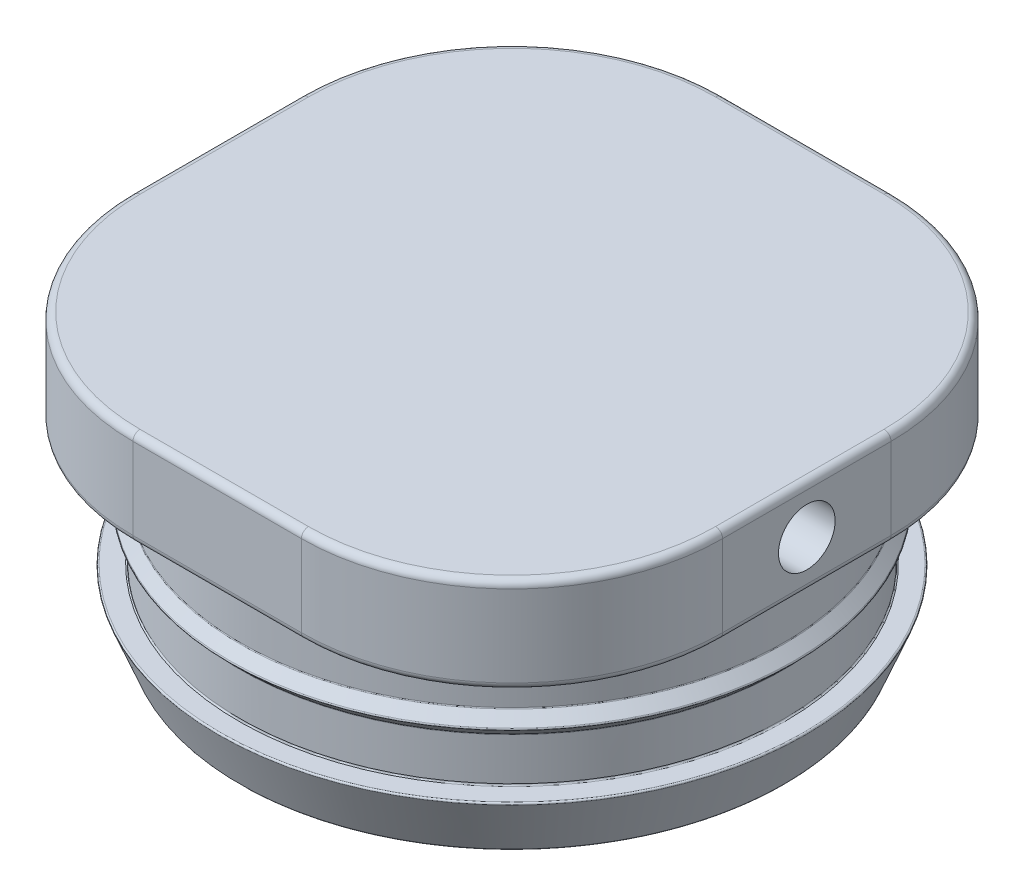
SolidWorks part; units mm, degrees
ref_plane "Front Plane" through (0, 0, 0) normal (0, 0, 1) x (1, 0, 0)
ref_plane "Top Plane" through (0, 0, 0) normal (0, 1, 0) x (1, 0, 0)
ref_plane "Right Plane" through (0, 0, 0) normal (1, 0, 0) x (0, 0, -1)
sketch "Sketch1" plane through (0, 0, 0) normal (0, 0, 1) x (1, 0, 0)
  line L3 (0, 0) -> (0, -6.8) construction
  line L4 (-21, 0) -> (0, 0)
  line L5 (-21, 0) -> (-21, -6.8)
  line L6 (-21, -6.8) -> (21, -6.8)
  line L7 (21, 0) -> (21, -6.8)
  line L8 (0, 0) -> (21, 0)
  dimension "D4" = 42
  dimension "D5" = 6.8
extrude "Boss-Extrude1" add sketch "Sketch1" along normal mid plane 42
sketch3d "3DSketch1" plane through (0, 0, 0) normal (0, 0, 1) x (1, 0, 0)
  dimension "D1" = 12.7
sketch "Sketch2" plane through (0, 0, 0) normal (0, 0, 1) x (1, 0, 0)
  line L0 (0, 9.544) -> (0, -9.544) construction
  line L1 (0, -6.8) -> (19.365, -6.8)
  line L4 (0, -19.5) -> (19.365, -19.5)
  line L10 (0, -19.5) -> (0, -6.8)
  line L11 (19.365, -19.5) -> (20.9525, -15.5312)
  line L12 (20.9525, -15.5312) -> (19.365, -15.5312)
  line L13 (19.365, -15.5312) -> (19.365, -12.3562)
  line L14 (19.365, -12.3562) -> (20.1588, -11.5625)
  line L15 (20.1588, -11.5625) -> (19.365, -10.7687)
  line L16 (20.1588, -11.5625) -> (19.365, -11.5625) construction
  line L17 (19.365, -10.7687) -> (19.365, -6.8)
  dimension "D1" = 38.73
  dimension "D2" = 12.7
  dimension "D3" = 1.5875
  dimension "D4" = 3.9688
  dimension "D5" = 0.7937
  dimension "D6" = 7.9375
  dimension "D7" = 6.8
revolve "Revolve1" add sketch "Sketch2" angle 360 about L0
sketch "Sketch3" plane through (0, -19.5, 0) normal (0, -1, 0) x (1, 0, 0)
  circle A0 centre (0, 0) radius 4
  dimension "D1" = 8
extrude "Cut-Extrude1" cut sketch "Sketch3" against normal blind 18.5 contours A0
hole_wizard "#10-32 Tapped Hole1" positions "Sketch4" profile "Sketch5" tap size "#10-32" standard "ANSI Inch" end condition up to next
sketch "Sketch4" plane through (21, 0, 0) normal (1, 0, 0) x (0, 0, -1)
  point P0 (0, -3.4)
  dimension "D1" = 3.4
cosmetic thread "Hole Thread1" parameters "D2"=4.826
sketch "Sketch5" plane through (21, -3.4, 0) normal (0, 1, 0) x (0, 0, -1)
  line L0 (0, 0) -> (0, 17)
  line L1 (0, 17) -> (2.0193, 17)
  line L2 (2.0193, 17) -> (2.0193, 0)
  line L5 (2.0193, 0) -> (0, 0)
  line L11 (0, -6.35) -> (0, 107.95) construction
  dimension "Thru Tap Drill Dia." = 4.0386
  dimension "Thru Tap Drill Depth" = 17
fillet "Fillet3" radius 0.1 8 edges at (-20.9525, -15.5313, 0) (-20.1588, -11.5625, 0) (4, -1, 0) (-19.365, -19.5, 0) (-19.365, -6.8, 0) (-19.365, -10.7688, 0) (-19.365, -12.3563, 0) (-19.365, -15.5313, 0)
chamfer "Chamfer1" distance 2 angle 60 1 edges at (4, -19.5, 0) first distance on face at (-19.2973, -19.5, 0)
fillet "Fillet6" radius 15 4 edges at (21, -3.4, -21) (-21, -3.4, -21) (-21, -3.4, 21) (21, -3.4, 21)
fillet "Fillet8" radius 0.5 16 edges at (-16.6066, -6.8, 16.6066) (-21, -6.8, 0) (-16.6066, -6.8, -16.6066) (0, -6.8, -21) (16.6066, -6.8, -16.6066) (21, -6.8, 0) (16.6066, -6.8, 16.6066) (16.6066, 0, 16.6066) (-16.6066, 0, 16.6066) (-21, 0, 0) (-16.6066, 0, -16.6066) (16.6066, 0, -16.6066) (0, -6.8, 21) (21, 0, 0) (0, 0, 21) (0, 0, -21)
fillet "Fillet9" radius 3.5 1 edges at (3.995, -5.4095, -0.1991)
